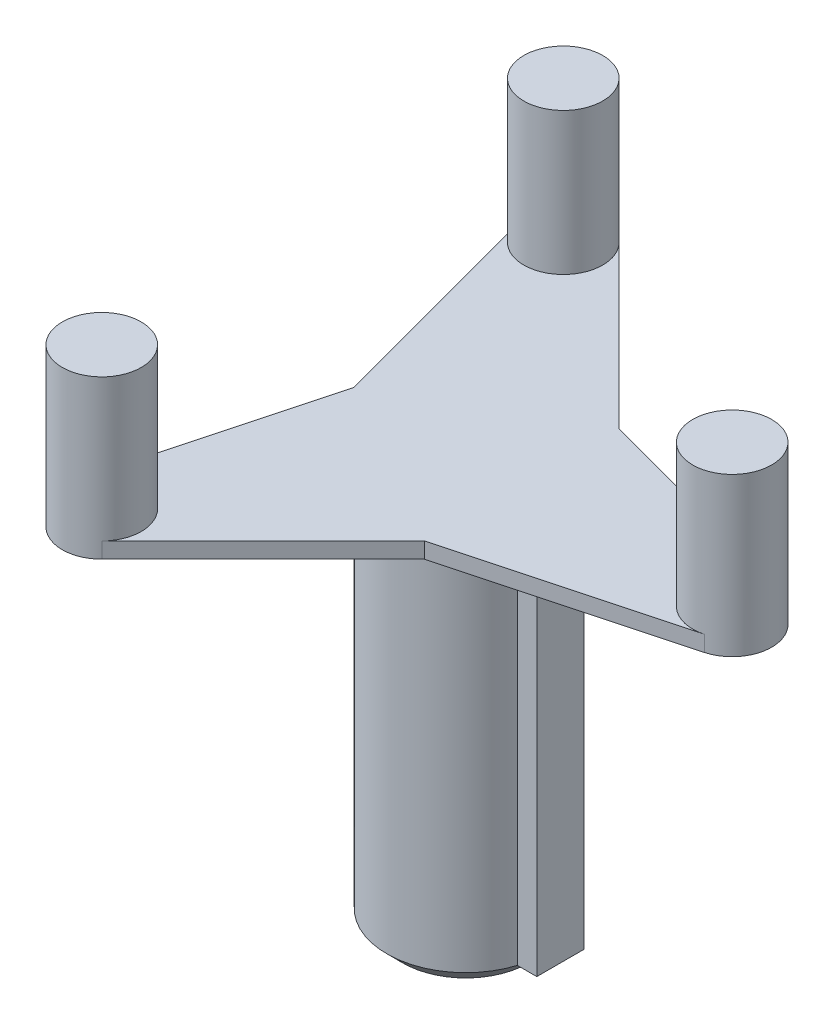
SolidWorks part; units mm, degrees
ref_plane "Front Plane" through (0, 0, 0) normal (0, 0, 1) x (1, 0, 0)
ref_plane "Top Plane" through (0, 0, 0) normal (0, 1, 0) x (1, 0, 0)
ref_plane "Right Plane" through (0, 0, 0) normal (1, 0, 0) x (0, 0, -1)
sketch "Sketch1" plane through (0, 0, 0) normal (0, 1, 0) x (1, 0, 0)
  circle A0 centre (0, 0) radius 33.75 construction
  circle A1 centre (0, 0) radius 28.75
  circle A2 centre (0, 0) radius 38.75
  dimension "D1" = 67.5
  dimension "D3" = 10
  dimension "D2" = 5
ref_axis "Axis1" through (0, 0, 0) along (0, 1, 0)
sketch "Sketch2" plane through (0, 0, 0) normal (0, 1, 0) x (1, 0, 0)
  circle A0 centre (33.75, 0) radius 5
  circle A1 centre (-16.875, -29.2284) radius 5
  circle A2 centre (-16.875, 29.2284) radius 5
  point P9 (0, 0)
  dimension "D2" = 10
  dimension "D1" = 33.75
  dimension "D3" = 3
extrude "Boss-Extrude2" add sketch "Sketch2" along normal blind 18
sketch "Sketch5" plane through (0, 0, 0) normal (0, 1, 0) x (1, 0, 0)
  line L0 (-13.3395, 32.7639) -> (7.1098, 12.3146)
  line L1 (7.1098, 12.3146) -> (35.0441, 4.8296)
  line L2 (35.0441, -4.8296) -> (7.1098, -12.3146)
  line L3 (7.1098, -12.3146) -> (-13.3395, -32.7639)
  line L4 (-21.7046, -27.9343) -> (-14.2197, 0)
  line L5 (-14.2197, 0) -> (-21.7046, 27.9343)
  circle A0 centre (-16.875, 29.2284) radius 5 construction
  circle A1 centre (33.75, 0) radius 5 construction
  arc A2 (35.0441, 4.8296) -> (35.0441, -4.8296) centre (33.75, 0) cw
  arc A3 (-13.3395, -32.7639) -> (-21.7046, -27.9343) centre (-16.875, -29.2284) cw
  arc A4 (-21.7046, 27.9343) -> (-13.3395, 32.7639) centre (-16.875, 29.2284) cw
  point P23 (0, 0)
  dimension "D2" = 3
  dimension "D1" = 150
extrude "Boss-Extrude3" add sketch "Sketch5" against normal blind 2 contours L2 L3 A3 L4 L5 A4 L0 L1 A2
sketch "Sketch6" plane through (0, -2, 0) normal (0, -1, 0) x (1, 0, 0)
  line L0 (9.5394, -3) -> (12, -3)
  line L3 (9.5394, 3) -> (12, 3)
  line L4 (12, -3) -> (12, 3)
  arc A0 (9.5394, 3) -> (9.5394, -3) centre (0, 0) ccw
  dimension "D1" = 20
extrude "Boss-Extrude4" add sketch "Sketch6" along normal blind 50
chamfer "Chamfer5" distance 2 angle 45 4 edges at (10.7697, -52, 3) (12, -52, 0) (10.7697, -52, -3) (-10, -52, 0)
scale "Scale1" scale about centroid uniform scaling yes scale factor 10
equation "\"ring_thickness\"=10"
equation "\"D3@Sketch1\"=\"ring_thickness\""
equation "\"D2@Sketch1\"=\"ring_thickness\"/2"
equation "\"planetary_bore_diameter\"=10"
equation "\"D2@Sketch2\"=\"planetary_bore_diameter\""
equation "\"ring_diameter\"= 22.5 + 45"
equation "\"D1@Sketch1\"=\"ring_diameter\""
equation "\"D1@Sketch2\"=\"ring_diameter\"/2"
